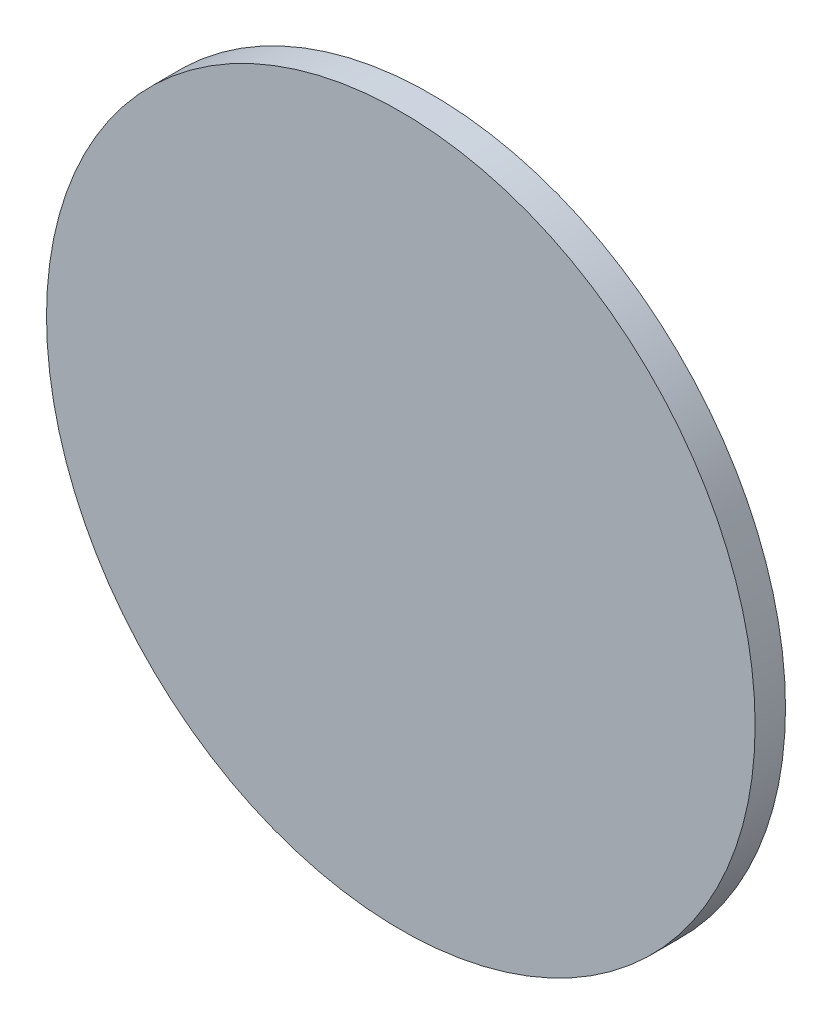
SolidWorks part; units mm, degrees
ref_plane "Front Plane" through (0, 0, 0) normal (0, 0, 1) x (1, 0, 0)
ref_plane "Top Plane" through (0, 0, 0) normal (0, 1, 0) x (1, 0, 0)
ref_plane "Right Plane" through (0, 0, 0) normal (1, 0, 0) x (0, 0, -1)
sketch "Sketch1" plane through (0, 0, 0) normal (0, 0, 1) x (1, 0, 0)
  circle A0 centre (0, 0) radius 350
  point P3 (0, 0)
  dimension "D1" = 700
extrude "Boss-Extrude1" add sketch "Sketch1" along normal blind 30
